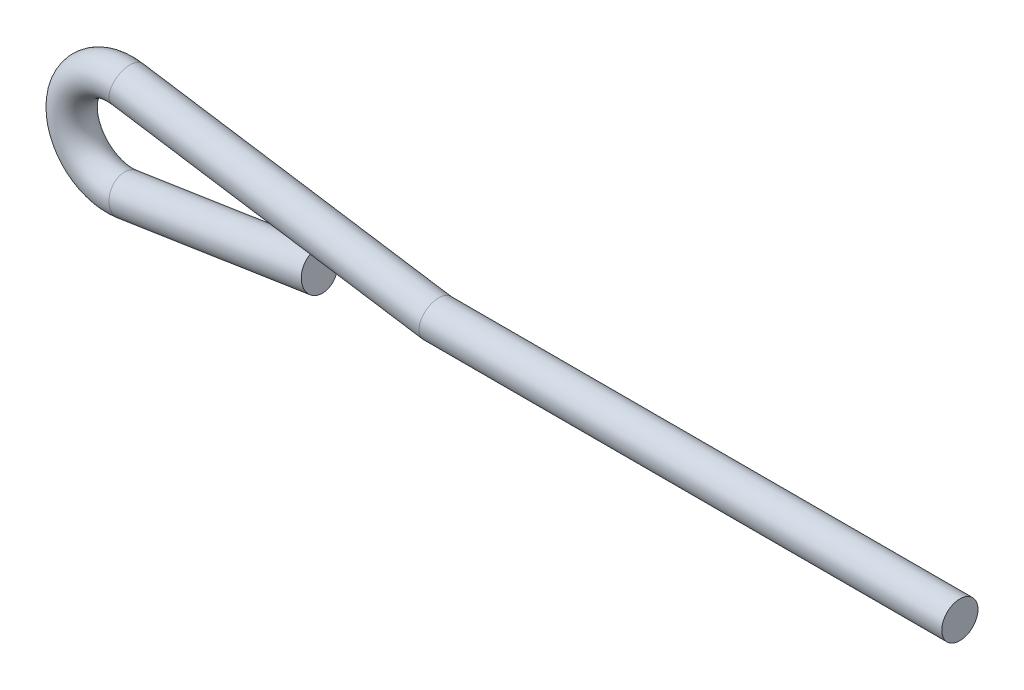
SolidWorks part; units mm, degrees
ref_plane "Front" through (0, 0, 0) normal (0, 0, 1) x (1, 0, 0)
ref_plane "Top" through (0, 0, 0) normal (0, 1, 0) x (1, 0, 0)
ref_plane "Right" through (0, 0, 0) normal (1, 0, 0) x (0, 0, -1)
sketch "Sketch2" plane through (-83.6956, -114.5384, 0) normal (0, 0, 1) x (0, 1, 0)
  line L0 (114.5384, -17.4214) -> (114.5384, -154.4214) construction
  line L1 (114.5384, -361.6956) -> (114.5384, -48.2156) construction
  line L2 (70.4012, -83.6956) -> (189.5185, -83.6956) construction
  line L3 (108.5384, -3.9296) -> (108.5384, -158.1438) construction
  line L4 (120.5384, -3.9296) -> (120.5384, -149.7804) construction
  line L5 (114.5384, -188.6956) -> (130.3516, -86.1337)
  line L6 (114.5384, -188.6956) -> (114.5384, -361.6956)
  line L7 (108.5384, -149.7804) -> (98.7253, -86.1337)
  arc A0 (130.3516, -86.1337) -> (98.7253, -86.1337) centre (114.5384, -83.6956) ccw
  circle A1 centre (114.5384, -83.6956) radius 10 construction
  arc A2 (92.5384, -83.6956) -> (136.5384, -83.6956) centre (114.5384, -83.6956) cw construction
  point P19 (120.5384, -149.7804)
  dimension "D3" = 16
  dimension "D4" = 22
  dimension "h" = 127
ref_plane "Plane1" through (66.0848, -6, 0) normal (-0.9883, -0.1524, 0) x (0, 0, 1)
sketch "Sketch1" plane through (66.0848, -6, 0) normal (-0.9883, -0.1524, 0) x (0, 0, 1)
  circle A0 centre (0, 0) radius 6
sweep "BaseBody" add profiles "Sketch1" path "Sketch2"
cosmetic thread "ThreadCosmetic1" [suppressed] parameters "b"=40, "d1"=10.106
sketch "Sketch3" plane through (0, 0, 0) normal (0, 0, 1) x (1, 0, 0)
  line L0 (277.5265, 6.947) -> (278.4735, 6.947)
  line L1 (278.4735, 6.947) -> (278.4735, 6)
  line L2 (278.4735, 6) -> (278, 5.1799)
  line L3 (278, 5.1799) -> (277.5265, 6)
  line L4 (277.5265, 6) -> (277.5265, 6.947)
  line L5 (278, -6) -> (278, 6) construction
  line L6 (278, 6) -> (105.4598, 6) construction
  dimension "D1" = 0.947
revolve "Cut-Revolve10" [suppressed] cut sketch "Sketch3" angle 360
pattern_linear "LPattern10" [suppressed] count 28 of bodies 102
equation "\"d1@Sketch2\" =\"d@Sketch1\""
equation "\"d2@Sketch2\" =\"d@Sketch1\"/ 2"
equation "\"D3@Sketch2\" =  ( \"D@Sketch2\" +\"d@Sketch1\" )  / 2"
equation "\"D4@Sketch2\" = \"D3@Sketch2\" + \"d@Sketch1\" / 2"
equation "\"D1@Sketch3\" =  ( \"d@Sketch1\" - \"d1@ThreadCosmetic1\" )  / 2"
equation "\"pitch@LPattern10\" = 1.5 * \"D1@Sketch3\""
equation "\"D1@LPattern10\" = \"b@ThreadCosmetic1\" / \"pitch@LPattern10\""
